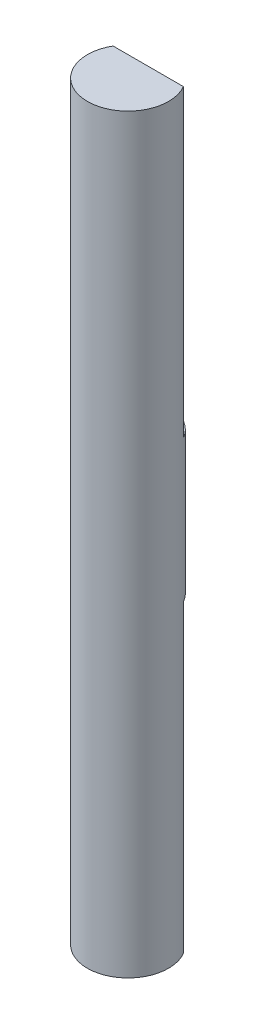
SolidWorks part; units mm, degrees
material "AISI 1045 Steel, cold drawn"
ref_plane "X-Y Datum" through (0, 0, 0) normal (0, 0, 1) x (1, 0, 0)
ref_plane "X-Z Datum" through (0, 0, 0) normal (0, 1, 0) x (1, 0, 0)
ref_plane "Y-Z Datum" through (0, 0, 0) normal (1, 0, 0) x (0, 0, -1)
sketch "Sketch1" plane through (0, 0, 0) normal (0, 1, 0) x (1, 0, 0)
  circle A0 centre (0, 0) radius 4
  dimension "D1" = 8
extrude "Boss-Extrude1" add sketch "Sketch1" along normal blind 37 and the other way blind 37
sketch "Sketch2" plane through (0, 37, 0) normal (0, 1, 0) x (1, 0, 0)
  line L0 (-3.4641, 2) -> (3.4641, 2)
  circle A0 centre (0, 0) radius 4 construction
  circle A1 centre (0, 0) radius 4
  circle M3 centre (0, 0) radius 4
  dimension "D2" = 8
  dimension "D1" = 2
extrude "Cut-Extrude1" cut sketch "Sketch2" against normal blind 30 contours L0 M3 region at (0, 37, -2.8201)
mirror "Mirror1" about plane through (0, 0, 0) normal (0, 1, 0) of "Cut-Extrude1"
